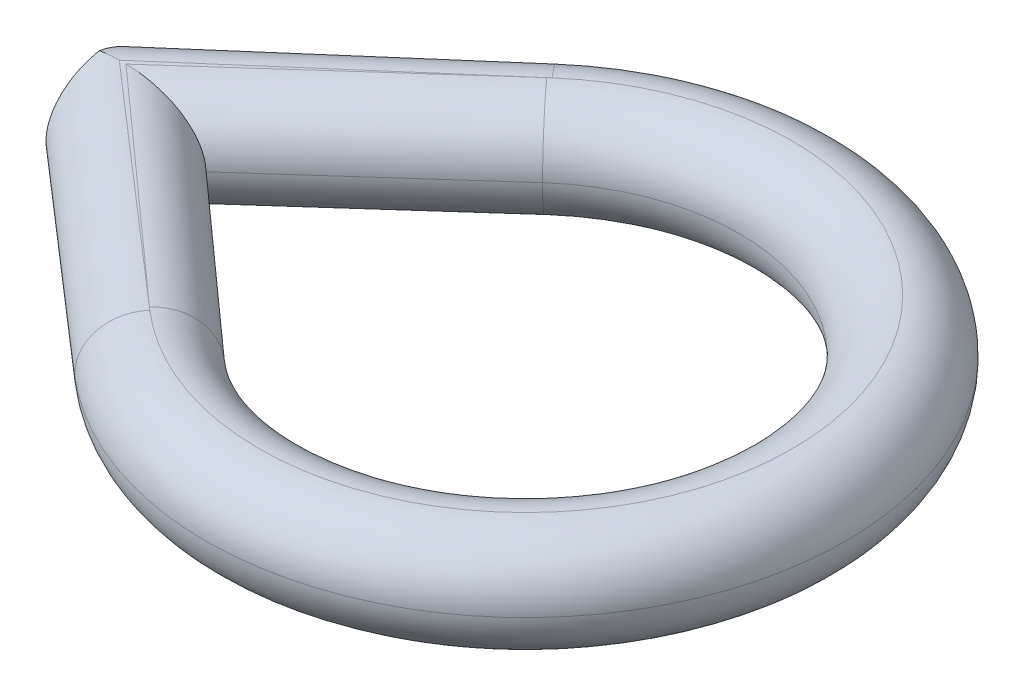
SolidWorks part; units mm, degrees
ref_plane "Front Plane" through (0, 0, 0) normal (0, 0, 1) x (1, 0, 0)
ref_plane "Top Plane" through (0, 0, 0) normal (0, 1, 0) x (1, 0, 0)
ref_plane "Right Plane" through (0, 0, 0) normal (1, 0, 0) x (0, 0, -1)
sketch "Sketch1" plane through (0, 0, 0) normal (0, 1, 0) x (1, 0, 0)
  line L0 (0, 0) -> (-8, 0) construction
  line L1 (-8, 0) -> (-8, 1)
  line L2 (-8, 0) -> (-8, -1)
  line L3 (-8, 1) -> (-3.9337, 4.5306)
  line L4 (-8, -1) -> (-3.9337, -4.5306)
  line L5 (-6, 0) -> (-2.6667, 2.9814)
  line L6 (-6, 0) -> (-2.6667, -2.9814)
  arc A0 (-2.6667, -2.9814) -> (-2.6667, 2.9814) centre (0, 0) ccw
  circle A1 centre (0, 0) radius 6 construction
  arc A2 (-3.9337, 4.5306) -> (-3.9337, -4.5306) centre (0, 0) cw
  point P13 (0, 0)
  dimension "D2" = 12
  dimension "D1" = 8
  dimension "D3" = 2
  dimension "D4" = 8
  dimension "D5" = 2
extrude "Boss-Extrude1" add sketch "Sketch1" along normal blind 1 and the other way blind 1 contours A2 L3 L1 L2 L4 A0 L6 L5 region at (-7.8156, 0, -0.5)
ref_point "SpringWireCentre"
fillet "Fillet1" radius 1 12 edges at (-5.9668, 1, -2.7653) (4, 1, 0) (6, 1, 0) (6, -1, 0) (-5.9668, -1, -2.7653) (-5.9668, -1, 2.7653) (-5.9668, 1, 2.7653) (-4.3333, -1, 1.4907) (4, -1, 0) (-4.3333, -1, -1.4907) (-4.3333, 1, 1.4907) (-4.3333, 1, -1.4907)
ref_point "CableCentre"
equation "\"SpringWireDiameter\"= 8"
equation "\"D1@Sketch1\"=\"SpringWireDiameter\""
equation "\"CableDiameter\"=2"
equation "\"D2@Sketch1\"=\"SpringWireDiameter\"+\"CableDiameter\"*2"
equation "\"D3@Sketch1\"=\"CableDiameter\""
equation "\"D5@Sketch1\"=\"CableDiameter\""
equation "\"D1@Boss-Extrude1\"=\"CableDiameter\"/2"
equation "\"D2@Boss-Extrude1\"=\"CableDiameter\"/2"
equation "\"D1@Fillet1\"=\"CableDiameter\"/2"
equation "\"D4@Sketch1\"=\"SpringWireDiameter\""
